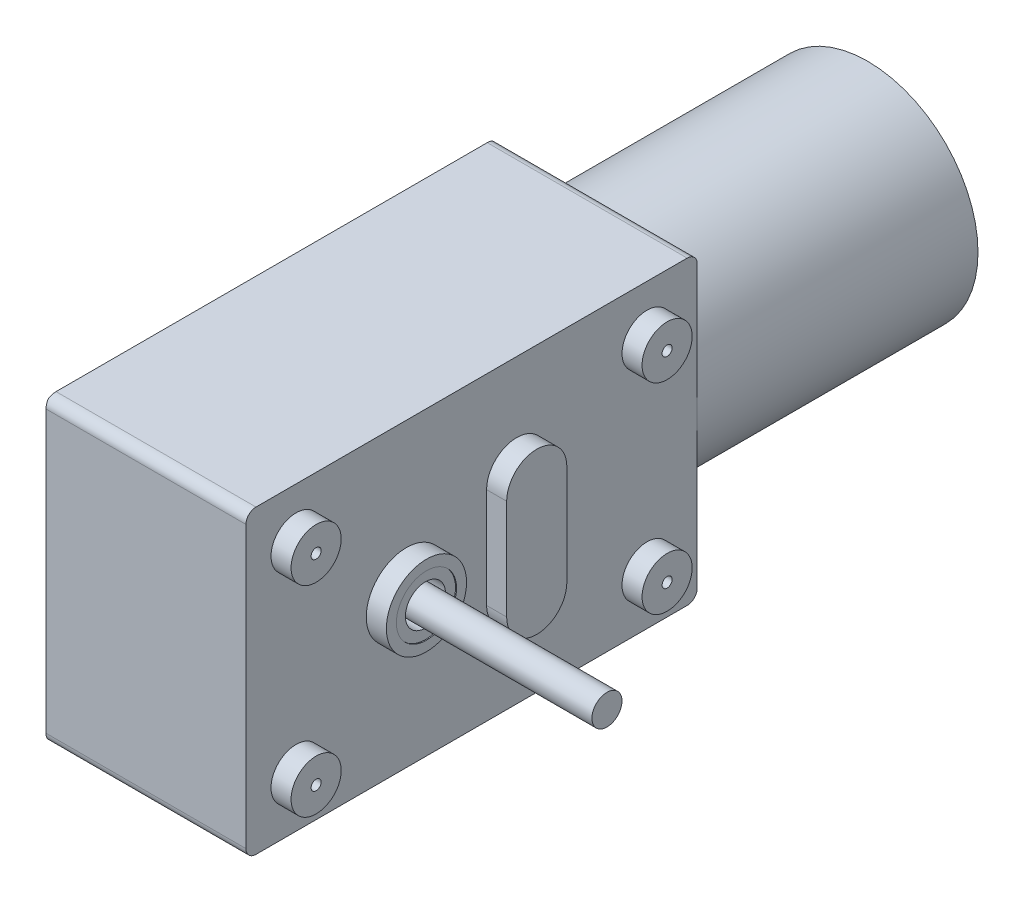
SolidWorks part; units mm, degrees
ref_plane "Front Plane" through (0, 0, 0) normal (0, 0, 1) x (1, 0, 0)
ref_plane "Top Plane" through (0, 0, 0) normal (0, 1, 0) x (1, 0, 0)
ref_plane "Right Plane" through (0, 0, 0) normal (1, 0, 0) x (0, 0, -1)
sketch "Sketch1" plane through (0, 0, 0) normal (1, 0, 0) x (0, 0, -1)
  line L1 (0, 30) -> (45, 30)
  line L2 (0, 30) -> (0, 0)
  line L3 (0, 0) -> (45, 0)
  line L4 (45, 30) -> (45, 0)
  dimension "D1" = 30
  dimension "D2" = 45
extrude "Boss-Extrude1" add sketch "Sketch1" against normal blind 21
sketch "Sketch2" plane through (0, 0, 0) normal (1, 0, 0) x (0, 0, -1)
  line L0 (45, 30) -> (0, 30) construction
  line L1 (0, 30) -> (0, 0) construction
  line L2 (0, 0) -> (45, 0) construction
  line L3 (45, 0) -> (45, 30) construction
  line L4 (45, 30) -> (0, 30) construction
  line L5 (0, 30) -> (0, 0) construction
  line L6 (0, 0) -> (45, 0) construction
  line L7 (45, 0) -> (45, 30) construction
  line L8 (40, 25) -> (5, 25) construction
  line L9 (5, 25) -> (5, 5) construction
  line L10 (5, 5) -> (40, 5) construction
  line L11 (40, 5) -> (40, 25) construction
  line L12 (16, 15) -> (5, 15) construction
  circle A0 centre (5, 25) radius 0.5
  circle A1 centre (5, 5) radius 0.5
  circle A2 centre (40, 5) radius 0.5
  circle A3 centre (40, 25) radius 0.5
  circle A4 centre (5, 25) radius 2.5
  circle A5 centre (5, 5) radius 2.5
  circle A6 centre (40, 5) radius 2.5
  circle A7 centre (40, 25) radius 2.5
  circle A8 centre (16, 15) radius 4
  circle A9 centre (16, 15) radius 3
  dimension "D2" = 1
  dimension "D4" = 8
  dimension "D5" = 16
  dimension "D1" = 5
  dimension "D3" = 2
  dimension "D6" = 1
extrude "Boss-Extrude2" add sketch "Sketch2" along normal blind 2
sketch "Sketch3" plane through (0, 0, 0) normal (1, 0, 0) x (0, 0, -1)
  circle A0 centre (16, 15) radius 3 construction
  circle A1 centre (16, 15) radius 3
  circle A2 centre (16, 15) radius 2
  dimension "D1" = 1
extrude "Boss-Extrude3" add sketch "Sketch3" along normal blind 1.9 separate body
sketch "Sketch4" plane through (0, 0, 0) normal (1, 0, 0) x (0, 0, -1)
  circle A0 centre (16, 15) radius 1.5
  dimension "D1" = 3
extrude "Boss-Extrude4" add sketch "Sketch4" along normal blind 20
sketch "Sketch6" plane through (0, 0, 0) normal (1, 0, 0) x (0, 0, -1)
  line L0 (45, 15) -> (27, 15) construction
  line L1 (45, 0) -> (45, 30) construction
  line L2 (27, 20) -> (27, 10) construction
  line L3 (30, 20) -> (30, 10)
  line L4 (24, 20) -> (24, 10)
  arc A0 (30, 20) -> (24, 20) centre (27, 20) ccw
  arc A1 (24, 10) -> (30, 10) centre (27, 10) ccw
  point P6 (27, 15)
  dimension "D2" = 3
  dimension "D1" = 18
  dimension "D3" = 10
extrude "Boss-Extrude5" add sketch "Sketch6" along normal blind 2
chamfer "Chamfer1" distance 5 angle 12 3 edges at (-21, 30, -22.5) (-21, 15, 0) (-21, 0, -22.5)
sketch "Sketch7" plane through (-21, 0, 0) normal (-1, 0, 0) x (0, 0, 1)
  line L0 (-5, 15) -> (-15, 15) construction
  line L1 (-5, 5) -> (-5, 25) construction
  circle A0 centre (-15, 15) radius 5
  dimension "D2" = 10
  dimension "D1" = 10
extrude "Boss-Extrude6" add sketch "Sketch7" along normal blind 0.8
fillet "Fillet2" radius 16 1 edges at (-21.8, 15, -10)
sketch "Sketch8" plane through (0, 0, -45) normal (0, 0, -1) x (-1, 0, 0)
  circle A0 centre (11, 16) radius 11
  dimension "D1" = 22
  dimension "D2" = 11
  dimension "D3" = 16
extrude "Boss-Extrude7" add sketch "Sketch8" along normal blind 28 separate body
sketch "Sketch9" plane through (0, 0, -73) normal (0, 0, -1) x (-1, 0, 0)
  circle A0 centre (11, 16) radius 11 construction
  circle A1 centre (11, 16) radius 11 construction
  circle A2 centre (11, 16) radius 10.8
  dimension "D1" = 0.2
extrude "Cut-Extrude1" cut sketch "Sketch9" against normal blind 1
sketch "Sketch10" plane through (0, 0, -72) normal (0, 0, -1) x (-1, 0, 0)
  circle A0 centre (11, 16) radius 2
  dimension "D1" = 4
extrude "Boss-Extrude8" add sketch "Sketch10" along normal blind 1
fillet "Fillet3" radius 0.5 1 edges at (-11, 18, -73)
fillet "Fillet4" radius 1 4 edges at (-9.9686, 0, -45) (-9.9686, 30, -45) (-9.9686, 0, 0) (-9.9686, 30, 0)
sketch "Sketch11" plane through (0, 0, 0) normal (0, -1, 0) x (1, 0, 0)
  line L0 (-31.2947, -28.042) -> (42.9396, -23.7715) construction
